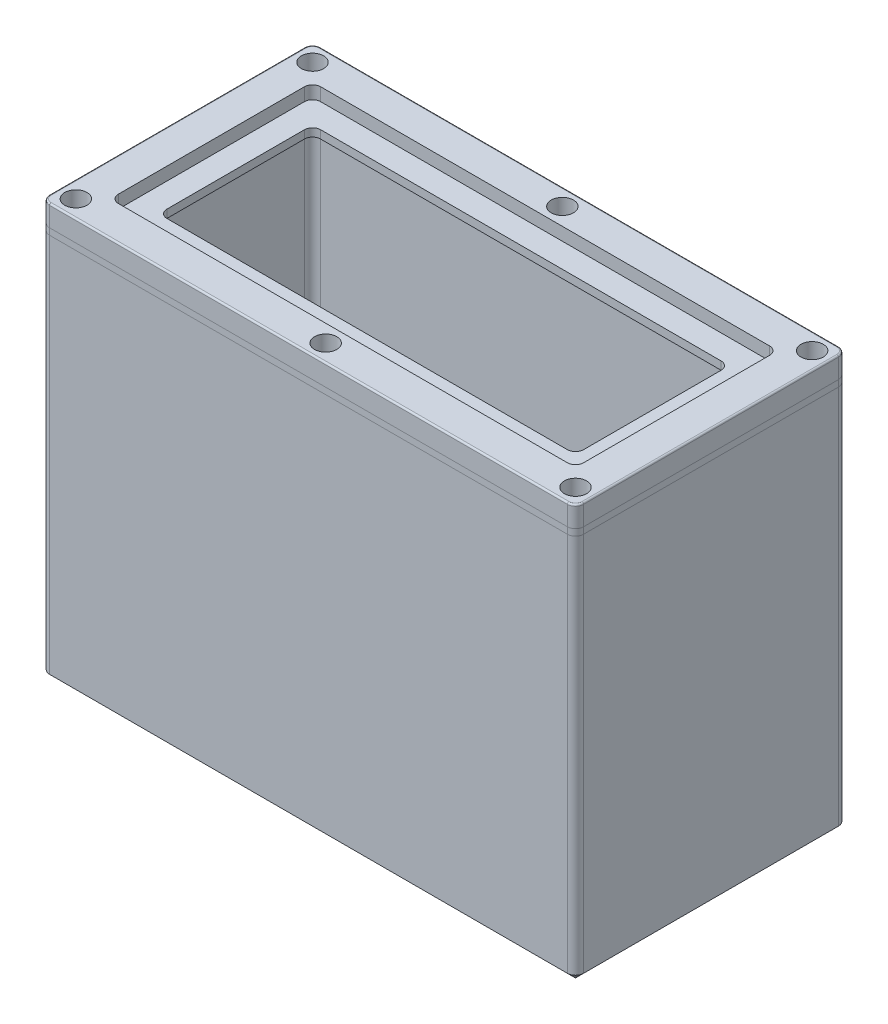
SolidWorks part; units mm, degrees
other "Body"
other "Gland"
other "Lid"
ref_plane "Front Plane" through (0, 0, 0) normal (0, 0, 1) x (1, 0, 0)
ref_plane "Top Plane" through (0, 0, 0) normal (0, 1, 0) x (1, 0, 0)
ref_plane "Right Plane" through (0, 0, 0) normal (1, 0, 0) x (0, 0, -1)
sketch "box_outline" plane through (0, 0, 0) normal (0, 1, 0) x (1, 0, 0)
  line L0 (-66, 33.5) -> (66, 33.5)
  line L1 (-57.5, -25) -> (57.5, -25)
  line L2 (-57.5, -25) -> (-57.5, 25)
  line L3 (-57.5, 25) -> (57.5, 25)
  line L4 (57.5, -25) -> (57.5, 25)
  line L5 (-57.5, -25) -> (57.5, 25) construction
  line L6 (-57.5, 25) -> (57.5, -25) construction
  line L7 (66, -33.5) -> (66, 33.5)
  line L8 (-66, -33.5) -> (66, -33.5)
  line L9 (-66, -33.5) -> (-66, 33.5)
  point P0 (0, 0)
  dimension "D2" = 115
  dimension "D3" = 50
  dimension "D1" = 8.5
sketch "motor_outline" plane through (0, 0, 0) normal (0, 1, 0) x (1, 0, 0)
  line L0 (-57.5, -25) -> (-57.5, 25) construction
  line L1 (-57.5, 25) -> (57.5, 25) construction
  line L2 (-57.5, -25) -> (57.5, -25) construction
  line L3 (57.5, -25) -> (57.5, 25) construction
  line L4 (-57.5, -25) -> (-57.5, 25)
  line L5 (-57.5, 25) -> (57.5, 25)
  line L6 (-57.5, -25) -> (57.5, -25)
  line L7 (57.5, -25) -> (57.5, 25)
  line L8 (45.9, -14) -> (5.9, 14) construction
  line L14 (55, 20) -> (-3.2, 20)
  line L15 (55, 20) -> (55, -20)
  line L16 (55, -20) -> (-3.2, -20)
  line L17 (-3.2, 20) -> (-3.2, -20)
  line L18 (55, 20) -> (-3.2, -20) construction
  line L19 (55, -20) -> (-3.2, 20) construction
  circle A0 centre (45.9, -14) radius 4.5
  circle A1 centre (5.9, -14) radius 4.5
  circle A2 centre (5.9, 14) radius 4.5
  circle A3 centre (45.9, 14) radius 4.5
  circle A4 centre (34.5, 0) radius 9.175
  circle A5 centre (45.9, -14) radius 2 construction
  circle A6 centre (34.5, 0) radius 4
  circle A7 centre (5.9, -14) radius 2 construction
  circle A8 centre (5.9, 14) radius 2 construction
  circle A9 centre (45.9, 14) radius 2 construction
  point P2 (25.9, 0)
  point P18 (25.9, 0)
  point P19 (-3.2, 0)
  point P22 (55, 0)
  point P29 (57.5, 0)
  dimension "D1" = 9
  dimension "D6" = 18.35
  dimension "D9" = 4
  dimension "D10" = 8
  dimension "D2" = 28
  dimension "D3" = 40
  dimension "D4" = 40
  dimension "D5" = 58.2
  dimension "D7" = 20.5
  dimension "D8" = 2.5
extrude "Boss-Extrude2" add sketch "box_outline" against normal blind 4 contours L0 L7 L8 L9
extrude "Boss-Extrude3" add sketch "box_outline<4>" along normal blind 92 contours L9 L8 L7 L0 L4 L1 L2 L3 region at (0, 0, -32.0197)
sketch "box_outline<4>" plane through (0, 0, 0) normal (0, 1, 0) x (1, 0, 0) same geometry as "box_outline"
extrude "Boss-Extrude4" add sketch "motor_outline" along normal blind 5 contours A3 | A2 | A1 | A0
extrude "Cut-Extrude1" cut sketch "motor_outline<3>" against normal through all both and the other way through all contours A6
sketch "motor_outline<3>" plane through (0, 0, 0) normal (0, 1, 0) x (1, 0, 0) same geometry as "motor_outline"
sketch "motor mounts" plane through (0, 5, 0) normal (0, 1, 0) x (1, 0, 0)
  circle A0 centre (45.9, 14) radius 2 construction
  circle A1 centre (5.9, 14) radius 2 construction
  circle A2 centre (5.9, -14) radius 2 construction
  circle A3 centre (45.9, -14) radius 2 construction
  circle A4 centre (45.9, 14) radius 2
  circle A5 centre (5.9, 14) radius 2
  circle A6 centre (5.9, -14) radius 2
  circle A7 centre (45.9, -14) radius 2
hole_wizard "M4 motor mounts" positions "Sketch17" profile "Sketch18" hole size "M4" standard "ISO" end condition through all
sketch "Sketch17" plane through (0, 5, 0) normal (0, 1, 0) x (1, 0, 0)
  point P0 (45.9, -14)
  point P3 (5.9, -14)
  point P6 (5.9, 14)
  point P9 (45.9, 14)
sketch "Sketch18" plane through (45.9, 5, 14) normal (1, 0, 0) x (0, 0, 1)
  line L0 (0, 0) -> (0, 9)
  line L1 (0, 9) -> (2.25, 9)
  line L2 (2.25, 9) -> (2.25, 0)
  line L5 (2.25, 0) -> (0, 0)
  line L11 (0, -6.35) -> (0, 107.95) construction
  dimension "Thru Hole Dia." = 4.5
  dimension "Thru Hole Depth" = 9
sketch "Sketch11" plane through (-66, 0, 0) normal (-1, 0, 0) x (0, 0, 1)
  line L0 (0, 62) -> (0, 92) construction
  line L4 (33.5, -4) -> (33.5, 92)
  line L5 (33.5, 92) -> (-33.5, 92)
  line L6 (-33.5, 92) -> (-33.5, -4)
  line L7 (-33.5, -4) -> (33.5, -4)
  line L8 (33.5, -4) -> (33.5, 92)
  line L9 (33.5, 92) -> (-33.5, 92)
  line L10 (-33.5, 92) -> (-33.5, -4)
  line L11 (-33.5, -4) -> (33.5, -4)
  circle A0 centre (0, 62) radius 4.5
  dimension "D3" = 9
  dimension "D2" = 30
  dimension "D1" = 0
extrude "cable gland hole" cut sketch "Sketch11" along direction (-1, 0, 0) on the side against the normal up to next (8.5 mm away) contours A0 region at (-66, 62, 0)
sketch "lid sketch" plane through (0, 92, 0) normal (0, 1, 0) x (1, 0, 0)
  line L0 (66, -33.5) -> (57.5, -25) construction
  line L1 (0, -25) -> (0, -33.5) construction
  line L2 (-57.5, -25) -> (57.5, -25) construction
  line L3 (-57.5, -25) -> (-66, -33.5) construction
  line L4 (-66, 33.5) -> (-66, -33.5)
  line L5 (-66, -33.5) -> (66, -33.5)
  line L6 (66, -33.5) -> (66, 33.5)
  line L7 (66, 33.5) -> (-66, 33.5)
  line L8 (-66, 33.5) -> (-66, -33.5)
  line L9 (-66, -33.5) -> (66, -33.5)
  line L10 (66, -33.5) -> (66, 33.5)
  line L11 (66, 33.5) -> (-66, 33.5)
  line L12 (57.5, 0) -> (66, 0) construction
  line L13 (57.5, -25) -> (57.5, 25) construction
  line L14 (-57.5, 0) -> (-66, 0) construction
  line L15 (-57.5, -25) -> (-57.5, 25) construction
  line L16 (-52.8, 0) -> (52.8, 0) construction
  circle A0 centre (61.75, -29.25) radius 2.5
  circle A1 centre (0, -29.25) radius 2.5
  circle A2 centre (-61.75, -29.25) radius 2.5
  circle A3 centre (61.75, 0) radius 2.5
  circle A4 centre (-61.75, 0) radius 2.5
  circle A5 centre (-61.75, 29.25) radius 2.5
  circle A6 centre (0, 29.25) radius 2.5
  circle A7 centre (61.75, 29.25) radius 2.5
  dimension "D2" = 5
  dimension "D1" = 0
hole_wizard "M5 Clearance Hole1" positions "3DSketch1" profile "Sketch3" hole size "M5" standard "ISO"
sketch3d "3DSketch1"
  point P0 (61.75, 92, 29.25)
  point P3 (0, 92, 29.25)
  point P6 (-61.75, 92, 29.25)
  point P12 (-61.75, 92, -29.25)
  point P15 (0, 92, -29.25)
  point P18 (61.75, 92, -29.25)
sketch "Sketch3" plane through (61.75, 92, 29.25) normal (1, 0, 0) x (0, 0, 1)
  line L0 (0, 0) -> (0, 5.6524)
  line L1 (0, 5.6524) -> (2.75, 4)
  line L2 (2.75, 4) -> (2.75, 0)
  line L5 (2.75, 0) -> (0, 0)
  line L10 (0, 5.6524) -> (-2.75, 4) construction
  line L11 (0, -6.35) -> (0, 107.95) construction
  dimension "Hole Dia." = 5.5
  dimension "Hole Depth" = 4
  dimension "Drill Angle" = 118
sketch "Sketch8" plane through (0, 92, 0) normal (0, 1, 0) x (1, 0, 0)
  line L4 (-66, 33.5) -> (-66, -33.5)
  line L5 (-66, -33.5) -> (66, -33.5)
  line L6 (66, -33.5) -> (66, 33.5)
  line L7 (66, 33.5) -> (-66, 33.5)
  line L8 (-66, 33.5) -> (-66, -33.5)
  line L9 (-66, -33.5) -> (66, -33.5)
  line L10 (66, -33.5) -> (66, 33.5)
  line L11 (66, 33.5) -> (-66, 33.5)
  circle M5 centre (61.75, -29.25) radius 2.75
  circle M6 centre (0, -29.25) radius 2.75
  circle M7 centre (-61.75, -29.25) radius 2.75
  circle M8 centre (-61.75, 29.25) radius 2.75
  circle M9 centre (0, 29.25) radius 2.75
  circle M10 centre (61.75, 29.25) radius 2.75
  line M11 (-66, 33.5) -> (-66, -33.5)
  line M12 (-66, -33.5) -> (66, -33.5)
  line M13 (66, -33.5) -> (66, 33.5)
  line M14 (66, 33.5) -> (-66, 33.5)
  line M15 (57.5, 25) -> (57.5, -25)
  line M16 (57.5, -25) -> (-57.5, -25)
  line M17 (-57.5, -25) -> (-57.5, 25)
  line M18 (-57.5, 25) -> (57.5, 25)
  dimension "D1" = 0
extrude "gland" add sketch "Sketch8" along normal blind 1.6 separate body contours M14 M11 M12 M13 M6 M8 M10 M18 M15 M16 M17 M9 M7 M5 region at (0, 92, -32.0197)
ref_plane "Plane2" through (0, 93.6, 0) normal (0, 1, 0) x (1, 0, 0)
sketch "Sketch1" plane through (0, 93.6, 0) normal (0, 1, 0) x (1, 0, 0)
  line L4 (-66, 33.5) -> (-66, -33.5)
  line L5 (-66, -33.5) -> (66, -33.5)
  line L6 (66, -33.5) -> (66, 33.5)
  line L7 (66, 33.5) -> (-66, 33.5)
  line L8 (-66, 33.5) -> (-66, -33.5)
  line L9 (-66, -33.5) -> (66, -33.5)
  line L10 (66, -33.5) -> (66, 33.5)
  line L11 (66, 33.5) -> (-66, 33.5)
  line L19 (57.5, 25) -> (57.5, -25) construction
  line L20 (57.5, -25) -> (-57.5, -25) construction
  line L21 (-57.5, 25) -> (57.5, 25) construction
  line L22 (-57.5, -25) -> (-57.5, 25) construction
  line L23 (51.5, -19) -> (51.5, 19)
  line L24 (51.5, 19) -> (-51.5, 19)
  line L25 (-51.5, -19) -> (51.5, -19)
  line L26 (-51.5, 19) -> (-51.5, -19)
  line L27 (51.5, -19) -> (51.5, 19)
  line L28 (51.5, 19) -> (-51.5, 19)
  line L29 (-51.5, -19) -> (51.5, -19)
  line L30 (-51.5, 19) -> (-51.5, -19)
  line L31 (57.5, 25) -> (57.5, -25)
  line L32 (57.5, -25) -> (-57.5, -25)
  line L33 (-57.5, 25) -> (57.5, 25)
  line L34 (-57.5, -25) -> (-57.5, 25)
  circle A0 centre (-61.75, 29.25) radius 2.5 construction
  circle A1 centre (-61.75, 0) radius 2.5 construction
  circle A2 centre (-61.75, -29.25) radius 2.5 construction
  circle A3 centre (0, -29.25) radius 2.5 construction
  circle A4 centre (0, 29.25) radius 2.5 construction
  circle A5 centre (61.75, 29.25) radius 2.5 construction
  circle A6 centre (61.75, -29.25) radius 2.5 construction
  circle A7 centre (61.75, 0) radius 2.5 construction
  circle A8 centre (-61.75, 29.25) radius 2.5
  circle A9 centre (-61.75, 0) radius 2.5
  circle A10 centre (-61.75, -29.25) radius 2.5
  circle A11 centre (0, -29.25) radius 2.5
  circle A12 centre (0, 29.25) radius 2.5
  circle A13 centre (61.75, 29.25) radius 2.5
  circle A14 centre (61.75, -29.25) radius 2.5
  circle A15 centre (61.75, 0) radius 2.5
  circle A16 centre (0, -29.25) radius 2.75
  circle A17 centre (61.75, -29.25) radius 2.75
  circle A18 centre (61.75, 0) radius 2.75
  circle A19 centre (61.75, 29.25) radius 2.75
  circle A20 centre (0, 29.25) radius 2.75
  circle A21 centre (-61.75, 29.25) radius 2.75
  circle A22 centre (-61.75, 0) radius 2.75
  circle A23 centre (-61.75, -29.25) radius 2.75
  dimension "D1" = 0
  dimension "D2" = 0.25
  dimension "D3" = 6
extrude "lid" add sketch "Sketch1" along normal blind 5.2 separate body contours A22 A18 | A18 A15 | A15 | A22 A9 | A9 region at (0, 93.6, -32.0197) region at (-61.75, 93.6, 0) region at (61.75, 93.6, 0) region at (59.0778, 93.6, 0) region at (-64.4222, 93.6, 0)
extrude "lid lip" add sketch "Sketch1<4>" along normal blind 2 contours L30 L28 L27 L29 region at (56.246, 93.6, 0)
sketch "Sketch1<4>" plane through (0, 93.6, 0) normal (0, 1, 0) x (1, 0, 0) same geometry as "Sketch1"
fillet "Fillet2" radius 2 12 edges at (51.5, 94.6, 19) (51.5, 94.6, -19) (-51.5, 94.6, 19) (-51.5, 94.6, -19) (-57.5, 97.2, -25) (-57.5, 97.2, 25) (57.5, 97.2, 25) (57.5, 97.2, -25) (66, 96.2, -33.5) (66, 96.2, 33.5) (-66, 96.2, -33.5) (-66, 96.2, 33.5)
fillet "Fillet3" radius 2 8 edges at (66, 44, 33.5) (-66, 44, 33.5) (-66, 44, -33.5) (66, 44, -33.5) (57.5, 46, 25) (-57.5, 46, 25) (57.5, 46, -25) (-57.5, 46, -25)
fillet "Fillet5" radius 2 8 edges at (66, 92.8, -33.5) (57.5, 92.8, -25) (57.5, 92.8, 25) (66, 92.8, 33.5) (-66, 92.8, -33.5) (-57.5, 92.8, -25) (-57.5, 92.8, 25) (-66, 92.8, 33.5)
chamfer "Chamfer1" distance 2 angle 45 8 edges at (66, -4, 0) (65.4142, -4, 32.9142) (65.4142, -4, -32.9142) (0, -4, 33.5) (0, -4, -33.5) (-65.4142, -4, 32.9142) (-65.4142, -4, -32.9142) (-66, -4, 0)
fillet "Fillet4" radius 2 8 edges at (-56.9142, 0, -24.4142) (-57.5, 0, 0) (-56.9142, 0, 24.4142) (0, 0, 25) (56.9142, 0, 24.4142) (57.5, 0, 0) (56.9142, 0, -24.4142) (0, 0, -25)
fillet "Fillet6" radius 0.4 8 edges at (65.4142, 98.8, -32.9142) (66, 98.8, 0) (65.4142, 98.8, 32.9142) (0, 98.8, 33.5) (-65.4142, 98.8, 32.9142) (-66, 98.8, 0) (-65.4142, 98.8, -32.9142) (0, 98.8, -33.5)
sketch "Sketch9" plane through (0, 95.6, 0) normal (0, 1, 0) x (1, 0, 0)
  line L4 (55.5, 25) -> (-55.5, 25)
  line L5 (-57.5, 23) -> (-57.5, -23)
  line L6 (-55.5, -25) -> (55.5, -25)
  line L7 (57.5, -23) -> (57.5, 23)
  line L8 (55.5, 25) -> (-55.5, 25)
  line L9 (-57.5, 23) -> (-57.5, -23)
  line L10 (-55.5, -25) -> (55.5, -25)
  line L11 (57.5, -23) -> (57.5, 23)
  arc A4 (-55.5, 25) -> (-57.5, 23) centre (-55.5, 23) ccw
  arc A5 (-57.5, -23) -> (-55.5, -25) centre (-55.5, -23) ccw
  arc A6 (55.5, -25) -> (57.5, -23) centre (55.5, -23) ccw
  arc A7 (57.5, 23) -> (55.5, 25) centre (55.5, 23) ccw
  arc A8 (-55.5, 25) -> (-57.5, 23) centre (-55.5, 23) ccw
  arc A9 (-57.5, -23) -> (-55.5, -25) centre (-55.5, -23) ccw
  arc A10 (55.5, -25) -> (57.5, -23) centre (55.5, -23) ccw
  arc A11 (57.5, 23) -> (55.5, 25) centre (55.5, 23) ccw
  dimension "D1" = 0
extrude "Boss-Extrude9" [suppressed] add sketch "Sketch9" along normal up to surface (3.2 mm away) separate body
